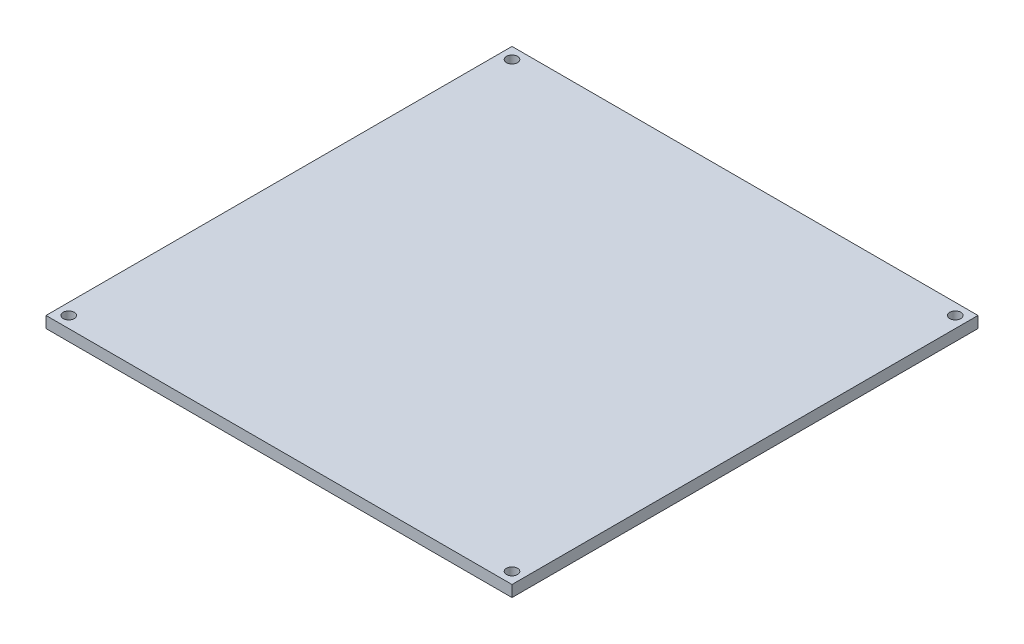
SolidWorks part; units mm, degrees
ref_plane "Front Plane" through (0, 0, 0) normal (0, 0, 1) x (1, 0, 0)
ref_plane "Top Plane" through (0, 0, 0) normal (0, 1, 0) x (1, 0, 0)
ref_plane "Right Plane" through (0, 0, 0) normal (1, 0, 0) x (0, 0, -1)
sketch "Sketch1" plane through (0, 0, 0) normal (0, 1, 0) x (1, 0, 0)
  line L0 (-50, 22.5543) -> (32, 22.5543) construction
  line L1 (32, 22.5543) -> (-9, 63.5543) construction
  line L2 (-9, -18.4457) -> (-9, -26.4272) construction
  line L3 (-50, 63.5543) -> (-50, -18.4457)
  line L4 (-50, 63.5543) -> (32, 63.5543)
  line L6 (-50, -18.4457) -> (32, -18.4457)
  line L7 (32, 63.5543) -> (32, -18.4457)
  line L13 (-48.7071, 62.2234) -> (-47.331, 60.8472) construction
  line L14 (-9, 63.5543) -> (-9, 22.5543) construction
  circle A2 centre (-48, 61.5543) radius 0.9735
  circle A6 centre (30, 61.5543) radius 0.9735
  circle A7 centre (-48, -16.4457) radius 0.9735
  circle A8 centre (30, -16.4457) radius 0.9735
  dimension "D3" = 2
  dimension "D1" = 82
  dimension "D2" = 41
  dimension "D4" = 2
extrude "Boss-Extrude1" add sketch "Sketch1" along normal blind 2
